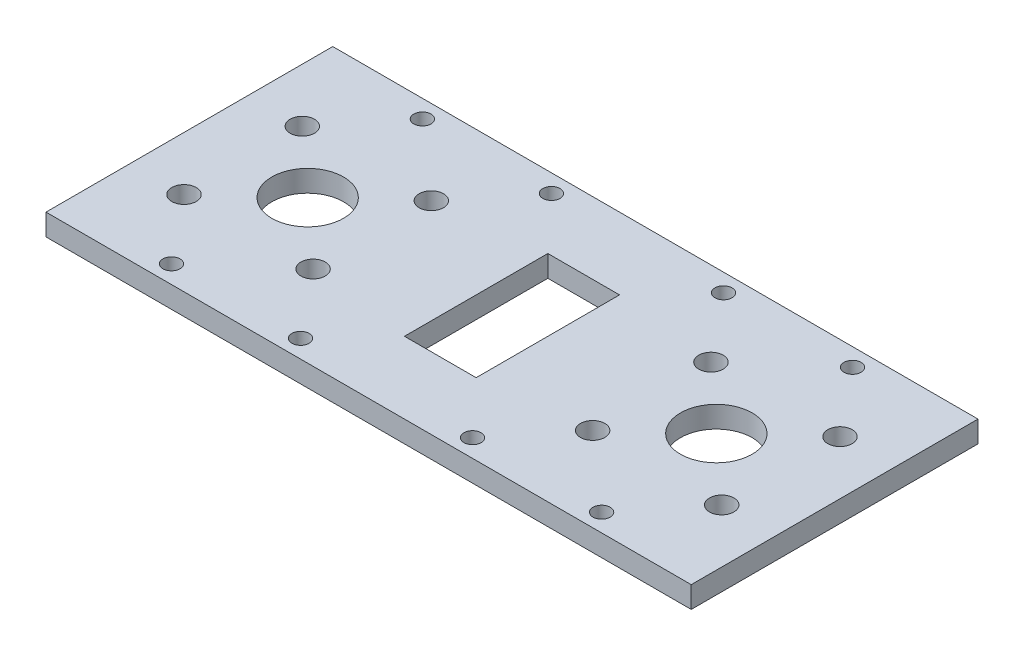
SolidWorks part; units mm, degrees
ref_plane "Front Plane" through (0, 0, 0) normal (0, 0, 1) x (1, 0, 0)
ref_plane "Top Plane" through (0, 0, 0) normal (0, 1, 0) x (1, 0, 0)
ref_plane "Right Plane" through (0, 0, 0) normal (1, 0, 0) x (0, 0, -1)
sketch "Sketch1" plane through (0, 0, 0) normal (0, 1, 0) x (1, 0, 0)
  line L0 (0, 0) -> (0, -14.43) construction
  line L1 (-45, 20) -> (45, 20)
  line L2 (-45, 20) -> (-45, -20)
  line L3 (-45, -20) -> (45, -20)
  line L4 (45, 20) -> (45, -20)
  line L5 (-45, 20) -> (45, -20) construction
  line L6 (-45, -20) -> (45, 20) construction
  line L7 (0, 0) -> (6.9805, 0) construction
  line L8 (-5, 10) -> (5, 10)
  line L9 (-5, 10) -> (-5, -10)
  line L10 (-5, -10) -> (5, -10)
  line L11 (5, 10) -> (5, -10)
  line L12 (-5, 10) -> (5, -10) construction
  line L13 (-5, -10) -> (5, 10) construction
  line L14 (0, 20) -> (0, -20) construction
  circle A0 centre (-28.5, 0) radius 5
  circle A1 centre (-37.5, 8.25) radius 1.7
  circle A2 centre (-19.5, 8.25) radius 1.7
  circle A3 centre (-19.5, -8.25) radius 1.7
  circle A4 centre (-37.5, -8.25) radius 1.7
  circle A26 centre (28.5, 0) radius 5
  circle A27 centre (19.5, 8.25) radius 1.7
  circle A28 centre (19.5, -8.25) radius 1.7
  circle A29 centre (37.5, -8.25) radius 1.7
  circle A30 centre (37.5, 8.25) radius 1.7
  point P0 (0, 0)
  dimension "D3" = 10
  dimension "D4" = 16.5
  dimension "D5" = 20
  dimension "D6" = 11.75
  dimension "D9" = 10
  dimension "D11" = 7.5
  dimension "D12" = 10
  dimension "D13" = 11.75
  dimension "D10" = 16.5
  dimension "D17" = 18
  dimension "D1" = 90
  dimension "D2" = 40
  dimension "D7" = 2
  dimension "D8" = 2
extrude "Boss-Extrude1" add sketch "Sketch1" along normal blind 3
sketch "Sketch3" plane through (0, 3, 0) normal (0, 1, 0) x (1, 0, 0)
  line L4 (-5, 10) -> (-5, -10) construction
  line L6 (45, 20) -> (-45, 20) construction
  line L10 (0, 0) -> (0, 13.8836) construction
  circle A1 centre (-12, 17.5) radius 1.2
  circle A2 centre (-12, -17.5) radius 1.2
  circle A4 centre (-30, 17.5) radius 1.2
  circle A5 centre (-30, -17.5) radius 1.2
  circle A8 centre (30, -17.5) radius 1.2
  circle A9 centre (30, 17.5) radius 1.2
  circle A10 centre (12, -17.5) radius 1.2
  circle A11 centre (12, 17.5) radius 1.2
  dimension "D1" = 2.5
  dimension "D2" = 7
  dimension "D3" = 35
  dimension "D5" = 2
  dimension "D6" = 2.4
  dimension "D7" = 2.4
  dimension "D4" = 7
extrude "Cut-Extrude1" cut sketch "Sketch3" against normal blind 10
